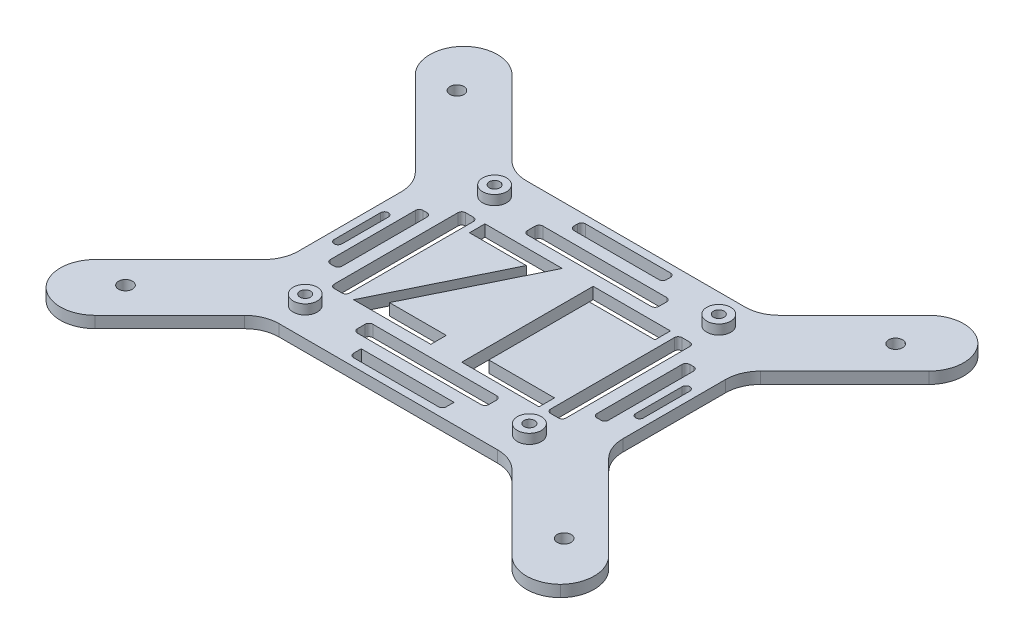
SolidWorks part; units mm, degrees
ref_plane "Front Plane" through (0, 0, 0) normal (0, 0, 1) x (1, 0, 0)
ref_plane "Top Plane" through (0, 0, 0) normal (0, 1, 0) x (1, 0, 0)
ref_plane "Right Plane" through (0, 0, 0) normal (1, 0, 0) x (0, 0, -1)
sketch "Sketch2" plane through (0, 0, 0) normal (0, 1, 0) x (1, 0, 0)
  line L16 (32, 32) -> (60.2843, 60.2843)
  line L17 (-42, 32) -> (42, 32)
  line L18 (-42, 32) -> (-42, -32)
  line L19 (-42, -32) -> (42, -32)
  line L20 (42, 32) -> (42, -32)
  line L21 (60.2843, 60.2843) -> (72.7843, 47.7843)
  line L22 (72.7843, 47.7843) -> (42, 17)
  line L23 (-86.7009, 0) -> (97.948, 0) construction
  line L24 (0, -48.5889) -> (0, 60.2843) construction
  line L25 (72.7843, -47.7843) -> (42, -17)
  line L26 (60.2843, -60.2843) -> (72.7843, -47.7843)
  line L27 (32, -32) -> (60.2843, -60.2843)
  line L28 (-60.2843, -60.2843) -> (-72.7843, -47.7843)
  line L29 (-72.7843, -47.7843) -> (-42, -17)
  line L30 (-32, -32) -> (-60.2843, -60.2843)
  line L31 (-72.7843, 47.7843) -> (-42, 17)
  line L32 (-60.2843, 60.2843) -> (-72.7843, 47.7843)
  line L33 (-32, 32) -> (-60.2843, 60.2843)
  dimension "D1" = 84
  dimension "D2" = 64
  dimension "D3" = 42
  dimension "D4" = 32
  dimension "D5" = 10
  dimension "D6" = 15
  dimension "D7" = 40
  dimension "D8" = 45
extrude "Boss-Extrude1" add sketch "Sketch2" along normal blind 3 contours L20 L17 L18 L19 | L30 L19 L18 L29 L28 | L22 L21 L16 L17 L20 | L19 L27 L26 L25 L20 | L17 L33 L32 L31 L18 region at (0, 0, 0) region at (53.3366, 0, -40.5461) region at (-53.3366, 0, -40.5461) region at (53.3366, 0, 40.5461) region at (-53.3366, 0, 40.5461)
sketch "Sketch3" plane through (0, 3, 0) normal (0, 1, 0) x (1, 0, 0)
  circle A0 centre (-29, 24.5) radius 3.1
  circle A1 centre (-29, -24.5) radius 3.1
  circle A2 centre (29, -24.5) radius 3.1
  circle A3 centre (29, 24.5) radius 3.1
  dimension "D1" = 6.2
  dimension "D2" = 6.2
  dimension "D3" = 6.2
  dimension "D4" = 6.2
  dimension "D5" = 58
  dimension "D6" = 49
  dimension "D7" = 58
  dimension "D8" = 49
  dimension "D9" = 29
  dimension "D10" = 24.5
  dimension "D11" = 29
  dimension "D12" = 29
extrude "Boss-Extrude2" add sketch "Sketch3" along normal blind 2.5
sketch "Sketch4" plane through (0, 5.5, 0) normal (0, 1, 0) x (1, 0, 0)
  circle A0 centre (-29, 24.5) radius 1.375
  circle A1 centre (-29, -24.5) radius 1.375
  circle A2 centre (29, -24.5) radius 1.375
  circle A3 centre (29, 24.5) radius 1.375
  dimension "D1" = 2.75
  dimension "D2" = 2.75
  dimension "D3" = 2.75
  dimension "D4" = 2.75
extrude "Cut-Extrude1" cut sketch "Sketch4" against normal through all
sketch "Sketch5" plane through (0, 3, 0) normal (0, 1, 0) x (1, 0, 0)
  circle A0 centre (-57.5, 43.25) radius 1.8
  circle A1 centre (56, 43.25) radius 1.8
  circle A2 centre (56.75, -43.25) radius 1.8
  circle A3 centre (-56.75, -43.25) radius 1.8
  point P8 (0, 0)
  dimension "D1" = 3.6
  dimension "D2" = 3.6
  dimension "D3" = 3.6
  dimension "D4" = 3.6
  dimension "D5" = 113.5
  dimension "D6" = 86.5
  dimension "D7" = 57.5
  dimension "D8" = 56.75
  dimension "D9" = 43.25
  dimension "D10" = 86.5
  dimension "D11" = 43.25
  dimension "D12" = 56.75
extrude "Cut-Extrude2" cut sketch "Sketch5" against normal through all
fillet "Fillet1" radius 9 8 edges at (-72.7843, 1.5, 47.7843) (-60.2843, 1.5, 60.2843) (60.2843, 1.5, 60.2843) (72.7843, 1.5, 47.7843) (72.7843, 1.5, -47.7843) (60.2843, 1.5, -60.2843) (-60.2843, 1.5, -60.2843) (-72.7843, 1.5, -47.7843)
fillet "Fillet2" radius 9 8 edges at (32, 1.5, 32) (-32, 1.5, 32) (-42, 1.5, 17) (-42, 1.5, -17) (-32, 1.5, -32) (32, 1.5, -32) (42, 1.5, 17) (42, 1.5, -17)
sketch "Sketch6" plane through (0, 3, 0) normal (0, 1, 0) x (1, 0, 0)
  line L0 (-24, 17) -> (-4, 17)
  line L1 (-4, 17) -> (-18.6993, -13)
  line L2 (-18.6993, -13) -> (-4, -13)
  line L3 (-4, -13) -> (-4, -17)
  line L4 (-4, -17) -> (-24, -17)
  line L5 (-24, -17) -> (-9.3007, 13)
  line L6 (-9.3007, 13) -> (-24, 13)
  line L7 (-24, 13) -> (-24, 17)
  line L8 (7, 13) -> (24, 13)
  line L9 (24, 13) -> (24, 17)
  line L10 (24, 17) -> (4, 17)
  line L11 (4, 17) -> (4, -17)
  line L12 (4, -17) -> (24, -17)
  line L13 (24, -17) -> (24, -13)
  line L14 (24, -13) -> (7, -13)
  line L15 (7, -13) -> (7, 13)
  line L16 (-28.2721, 32) -> (28.2721, 32) construction
  line L17 (-28.2721, -32) -> (28.2721, -32) construction
  line L18 (-42, 13.2721) -> (-42, -13.2721) construction
  line L19 (42, 13.2721) -> (42, -13.2721) construction
  point P18 (-14, -17)
  point P23 (24, 15)
  dimension "D1" = 15
  dimension "D2" = 15
  dimension "D3" = 4
  dimension "D4" = 4
  dimension "D5" = 4
  dimension "D6" = 15
  dimension "D7" = 18
  dimension "D8" = 18
  dimension "D9" = 3
  dimension "D10" = 3
  dimension "D11" = 20
  dimension "D12" = 20
  dimension "D13" = 18
  dimension "D14" = 20
  dimension "D15" = 18
extrude "Cut-Extrude3" cut sketch "Sketch6" against normal through all
sketch "Sketch7" plane through (0, 3, 0) normal (0, 1, 0) x (1, 0, 0)
  line L0 (-42, 13.2721) -> (-42, -13.2721) construction
  line L1 (-40, 7) -> (-38, 7)
  line L2 (-40, 7) -> (-40, -7)
  line L3 (-40, -7) -> (-38, -7)
  line L4 (-38, 7) -> (-38, -7)
  line L5 (-36, 12) -> (-33, 12)
  line L6 (-36, 12) -> (-36, -12)
  line L7 (-36, -12) -> (-33, -12)
  line L8 (-33, 12) -> (-33, -12)
  line L9 (-30, 17) -> (-26, 17)
  line L10 (-30, 17) -> (-30, -17)
  line L11 (-30, -17) -> (-26, -17)
  line L12 (-26, 17) -> (-26, -17)
  line L17 (-12, 30) -> (12, 30)
  line L18 (-12, 30) -> (-12, 27)
  line L19 (-12, 27) -> (12, 27)
  line L20 (12, 30) -> (12, 27)
  line L21 (-17, 24) -> (17, 24)
  line L22 (-17, 24) -> (-17, 20)
  line L23 (-17, 20) -> (17, 20)
  line L24 (17, 24) -> (17, 20)
  line L25 (-28.2721, 32) -> (28.2721, 32) construction
  line L26 (0, -43.333) -> (0, 45.6442) construction
  line L27 (-61.1352, 0) -> (57.0296, 0) construction
  line L28 (-17, -20) -> (17, -20)
  line L29 (17, -24) -> (17, -20)
  line L30 (-17, -24) -> (17, -24)
  line L31 (-17, -24) -> (-17, -20)
  line L32 (-12, -27) -> (12, -27)
  line L33 (12, -30) -> (12, -27)
  line L34 (-12, -30) -> (12, -30)
  line L35 (-12, -30) -> (-12, -27)
  line L36 (30, -17) -> (26, -17)
  line L37 (26, 17) -> (26, -17)
  line L38 (30, 17) -> (26, 17)
  line L39 (30, 17) -> (30, -17)
  line L40 (36, -12) -> (33, -12)
  line L41 (33, 12) -> (33, -12)
  line L42 (36, 12) -> (33, 12)
  line L43 (36, 12) -> (36, -12)
  line L44 (40, -7) -> (38, -7)
  line L45 (38, 7) -> (38, -7)
  line L46 (40, 7) -> (38, 7)
  line L47 (40, 7) -> (40, -7)
  dimension "D1" = 14
  dimension "D2" = 2
  dimension "D3" = 3
  dimension "D4" = 24
  dimension "D5" = 4
  dimension "D6" = 34
  dimension "D7" = 2
  dimension "D8" = 12
  dimension "D9" = 3
  dimension "D10" = 15
  dimension "D11" = 5
  dimension "D12" = 5
  dimension "D13" = 34
  dimension "D14" = 4
  dimension "D15" = 8
  dimension "D16" = 25
  dimension "D17" = 3
  dimension "D18" = 3
  dimension "D19" = 5
  dimension "D20" = 5
extrude "Cut-Extrude4" cut sketch "Sketch7" against normal through all
fillet "Fillet3" radius 1 38 edges at (-12, 1.5, -27) (12, 1.5, -27) (17, 1.5, -20) (-17, 1.5, -20) (-17, 1.5, -24) (17, 1.5, -24) (12, 1.5, -30) (-12, 1.5, -30) (-17, 1.5, 20) (17, 1.5, 20) (17, 1.5, 24) (12, 1.5, 30) (-12, 1.5, 30) (-17, 1.5, 24) (30, 1.5, 17) (36, 1.5, 12) (40, 1.5, 7) (38, 1.5, 7) (33, 1.5, 12) (26, 1.5, 17) (26, 1.5, -17) (33, 1.5, -12) (38, 1.5, -7) (30, 1.5, -17) (36, 1.5, -12) (40, 1.5, -7) (-30, 1.5, 17) (-26, 1.5, 17) (-30, 1.5, -17) (-26, 1.5, -17) (-33, 1.5, -12) (-36, 1.5, -12) (-33, 1.5, 12) (-36, 1.5, 12) (-38, 1.5, 7) (-40, 1.5, 7) (-38, 1.5, -7) (-40, 1.5, -7)
